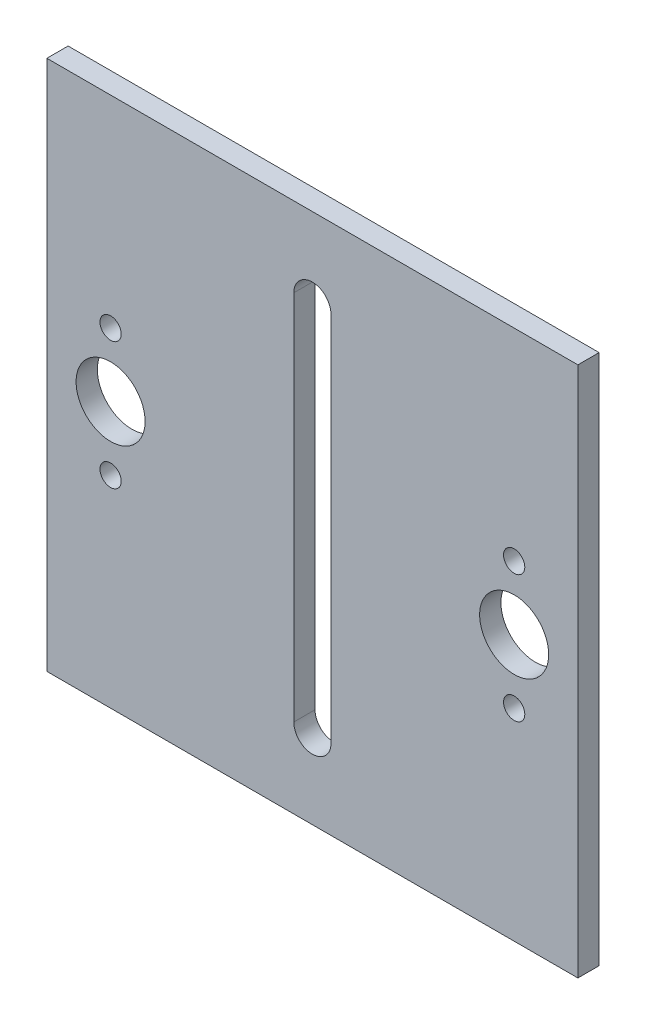
SolidWorks part; units mm, degrees
ref_plane "Front Plane" through (0, 0, 0) normal (0, 0, 1) x (1, 0, 0)
ref_plane "Top Plane" through (0, 0, 0) normal (0, 1, 0) x (1, 0, 0)
ref_plane "Right Plane" through (0, 0, 0) normal (1, 0, 0) x (0, 0, -1)
sketch "Sketch1" plane through (0, 0, 0) normal (0, 0, 1) x (1, 0, 0)
  line L1 (0, 0) -> (50, 0)
  line L2 (0, 0) -> (0, 50)
  line L3 (0, 50) -> (50, 50)
  line L4 (50, 0) -> (50, 50)
  dimension "D1" = 50
  dimension "D2" = 50
extrude "plate_body" add sketch "Sketch1" along normal blind 2
sketch "Sketch2" plane through (0, 0, 2) normal (0, 0, 1) x (1, 0, 0)
  line L0 (50, 50) -> (0, 50) construction
  line L1 (0, 50) -> (0, 0) construction
  circle A0 centre (6, 25) radius 3.25
  circle A1 centre (44, 25) radius 3.25
  dimension "D1" = 38
  dimension "D2" = 6.5
  dimension "D3" = 6.5
  dimension "D4" = 25
  dimension "D5" = 6
  dimension "D6" = 25
extrude "shaft_bearings" cut sketch "Sketch2" against normal through all
sketch "Sketch3" plane through (0, 0, 2) normal (0, 0, 1) x (1, 0, 0)
  line L0 (0, 50) -> (0, 0) construction
  line L1 (0, 50) -> (0, 0) construction
  line L2 (50, 0) -> (50, 50) construction
  circle A0 centre (6, 31) radius 1
  circle A1 centre (6, 19) radius 1
  circle A2 centre (44, 31) radius 1
  circle A3 centre (44, 19) radius 1
  circle A4 centre (6, 25) radius 3.25 construction
  circle A5 centre (44, 25) radius 3.25 construction
  dimension "D1" = 2
  dimension "D2" = 2
  dimension "D3" = 6
  dimension "D4" = 6
  dimension "D5" = 12
  dimension "D6" = 6
  dimension "D7" = 2
  dimension "D8" = 2
  dimension "D9" = 12
  dimension "D10" = 6
  dimension "D11" = 6
  dimension "D12" = 6
extrude "bearing_bolt_holes" cut sketch "Sketch3" against normal through all
sketch "Sketch4" plane through (0, 0, 2) normal (0, 0, 1) x (1, 0, 0)
  line L0 (25, 42.5) -> (25, 7.5) construction
  line L1 (26.75, 42.5) -> (26.75, 7.5)
  line L2 (23.25, 42.5) -> (23.25, 7.5)
  line L3 (0, 50) -> (0, 0) construction
  line L4 (0, 0) -> (50, 0) construction
  arc A0 (26.75, 42.5) -> (23.25, 42.5) centre (25, 42.5) ccw
  arc A1 (23.25, 7.5) -> (26.75, 7.5) centre (25, 7.5) ccw
  point P2 (25, 25)
  dimension "D4" = 7.5
  dimension "D1" = 3.5
  dimension "D2" = 35
  dimension "D3" = 25
extrude "Cut-Extrude1" cut sketch "Sketch4" against normal through all
